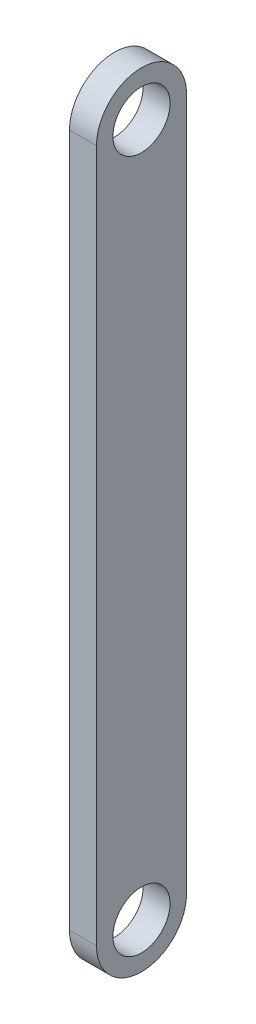
SolidWorks part; units mm, degrees
material "Acrylic (Medium-high impact)"
ref_plane "Alzado" through (0, 0, 0) normal (0, 0, 1) x (1, 0, 0)
ref_plane "Planta" through (0, 0, 0) normal (0, 1, 0) x (1, 0, 0)
ref_plane "Vista lateral" through (0, 0, 0) normal (1, 0, 0) x (0, 0, -1)
sketch "Sketch3" plane through (0, 0, 0) normal (1, 0, 0) x (0, 0, -1)
  line L1 (-5, -43.5) -> (5, -43.5)
  line L2 (-5, -43.5) -> (-5, 43.5)
  line L3 (-5, 43.5) -> (5, 43.5)
  line L4 (5, -43.5) -> (5, 43.5)
  line L5 (-5, -43.5) -> (5, 43.5) construction
  line L6 (-5, 43.5) -> (5, -43.5) construction
  point P0 (0, 0)
  dimension "D1" = 87
  dimension "D2" = 10
extrude "Boss-Extrude1" add sketch "Sketch3" along normal blind 3 contours L3 L4 L1 L2
sketch "Sketch4" plane through (3, 0, 0) normal (1, 0, 0) x (0, 0, -1)
  line L0 (0, 0) -> (0, -43.5) construction
  line L1 (-5, -43.5) -> (5, -43.5) construction
  line L2 (0, 0) -> (0, 43.5) construction
  line L3 (-5, 43.5) -> (5, 43.5) construction
  line L4 (0, 0) -> (0, 38.5) construction
  line L5 (0, 0) -> (0, -38.5) construction
  circle A0 centre (0, 38.5) radius 3.175
  circle A1 centre (0, -38.5) radius 3.175
  dimension "D1" = 38.5
  dimension "D2" = 38.5
extrude "Cut-Extrude1" cut sketch "Sketch4" against normal blind 5
fillet "Fillet1" 2 edges at (1.5, 43.5, 5) (1.5, 43.5, -5) type full round first side face at (1.5, 0, 5) second side face at (1.5, 0, -5) middle face at (1.5, 43.5, 0)
fillet "Fillet2" 2 edges at (1.5, -43.5, -5) (1.5, -43.5, 5) type full round first side face at (1.5, -2.5, -5) second side face at (1.5, -2.5, 5) middle face at (1.5, -43.5, 0)
